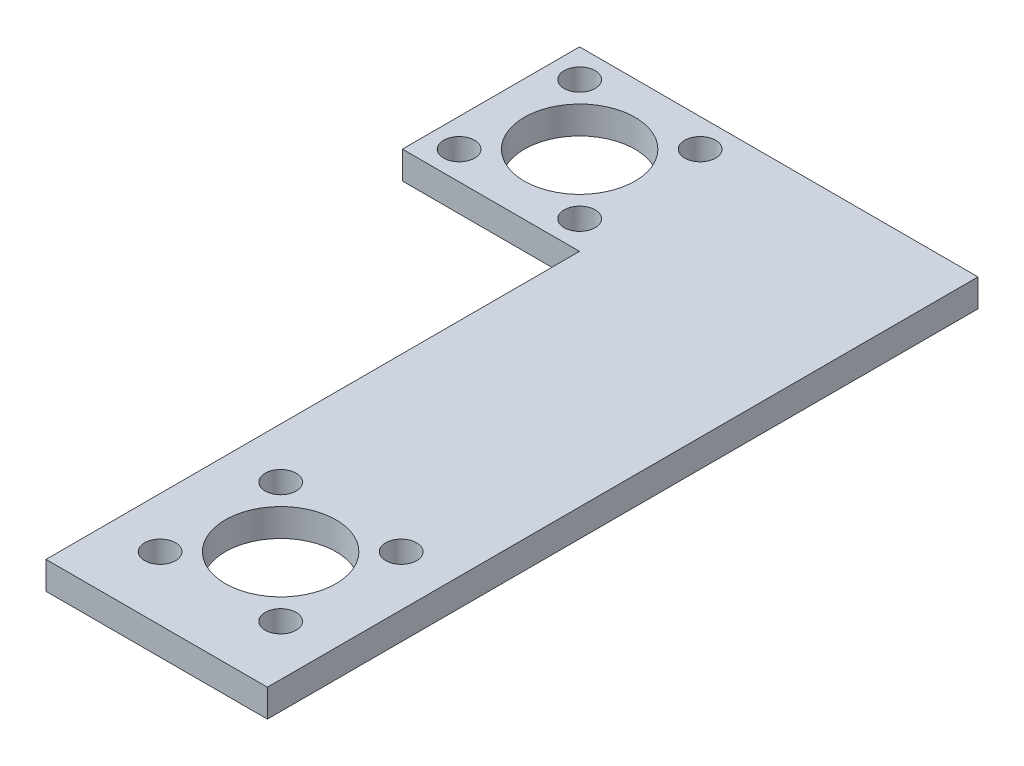
SolidWorks part; units mm, degrees
ref_plane "Front Plane" through (0, 0, 0) normal (0, 0, 1) x (1, 0, 0)
ref_plane "Top Plane" through (0, 0, 0) normal (0, 1, 0) x (1, 0, 0)
ref_plane "Right Plane" through (0, 0, 0) normal (1, 0, 0) x (0, 0, -1)
sketch "Sketch1" plane through (0, 0, 0) normal (0, 1, 0) x (1, 0, 0)
  line L0 (0, 0) -> (-45.72, 0)
  line L1 (0, 0) -> (0, -81.534)
  line L2 (-45.72, 0) -> (-45.72, -20.32)
  line L3 (0, -81.534) -> (-25.4, -81.534)
  line L4 (-25.4, -81.534) -> (-25.4, -20.32)
  line L5 (-45.72, -20.32) -> (-25.4, -20.32)
  dimension "D1" = 20.32
  dimension "D2" = 61.214
extrude "Boss-Extrude1" add sketch "Sketch1" along normal blind 3.175
sketch "Sketch2" plane through (0, 3.175, 0) normal (0, 1, 0) x (1, 0, 0)
  line L0 (-45.72, 0) -> (-45.72, -20.32) construction
  line L1 (-45.72, -10.16) -> (-25.3695, -10.16) construction
  line L2 (-35.5448, -10.16) -> (-42.4596, -17.0748) construction
  line L3 (-35.5448, -10.16) -> (-42.4596, -3.2452) construction
  line L4 (-35.5448, -10.16) -> (-28.63, -3.2452) construction
  line L5 (-35.5448, -10.16) -> (-28.63, -17.0748) construction
  circle A0 centre (-42.4596, -3.2452) radius 1.778
  circle A1 centre (-28.63, -3.2452) radius 1.778
  circle A2 centre (-28.63, -17.0748) radius 1.778
  circle A3 centre (-42.4596, -17.0748) radius 1.778
  circle A4 centre (-35.5448, -10.16) radius 6.35
extrude "Cut-Extrude1" cut sketch "Sketch2" against normal blind 3.175
sketch "Sketch7" plane through (0, 3.175, 0) normal (0, 1, 0) x (1, 0, 0)
  line L0 (-12.7, -57.15) -> (-12.7, -77.47) construction
  line L2 (-12.7, -57.15) -> (0, -57.15) construction
  line L3 (0, -81.534) -> (0, 0) construction
  line L4 (-12.7, -67.31) -> (-5.7852, -74.2248) construction
  line L5 (-12.7, -67.31) -> (-19.6148, -74.2248) construction
  line L6 (-12.7, -67.31) -> (-19.6148, -60.3952) construction
  line L7 (-12.7, -67.31) -> (-5.7852, -60.3952) construction
  circle A0 centre (-12.7, -67.31) radius 6.35
  circle A1 centre (-5.7852, -60.3952) radius 1.778
  circle A2 centre (-5.7852, -74.2248) radius 1.778
  circle A3 centre (-19.6148, -74.2248) radius 1.778
  circle A4 centre (-19.6148, -60.3952) radius 1.778
extrude "Cut-Extrude3" cut sketch "Sketch7" against normal blind 3.175
